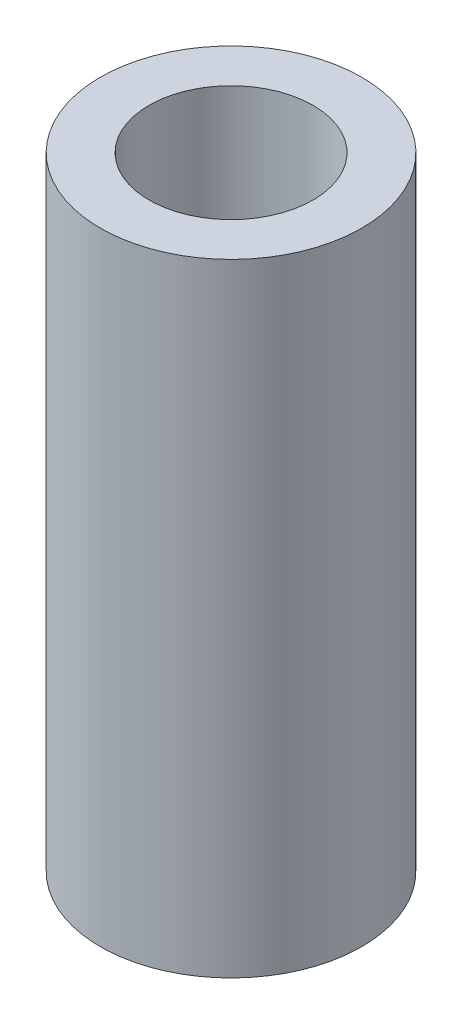
SolidWorks part; units mm, degrees
ref_plane "Front Plane" through (0, 0, 0) normal (0, 0, 1) x (1, 0, 0)
ref_plane "Top Plane" through (0, 0, 0) normal (0, 1, 0) x (1, 0, 0)
ref_plane "Right Plane" through (0, 0, 0) normal (1, 0, 0) x (0, 0, -1)
sketch "Sketch1" plane through (0, 0, 0) normal (0, 1, 0) x (1, 0, 0)
  circle A0 centre (0, 0) radius 16.6751
  circle A1 centre (0, 0) radius 10.4648
  dimension "D1" = 20.9296
  dimension "D2" = 33.3502
extrude "Boss-Extrude1" add sketch "Sketch1" along normal mid plane 79.375
sketch "Sketch2" plane through (0, 0, 0) normal (1, 0, 0) x (0, 0, -1)
  circle A0 centre (0, 0) radius 13.5001
  circle A1 centre (0, 0) radius 7.8994
  dimension "D1" = 27.0002
  dimension "D2" = 15.7988
